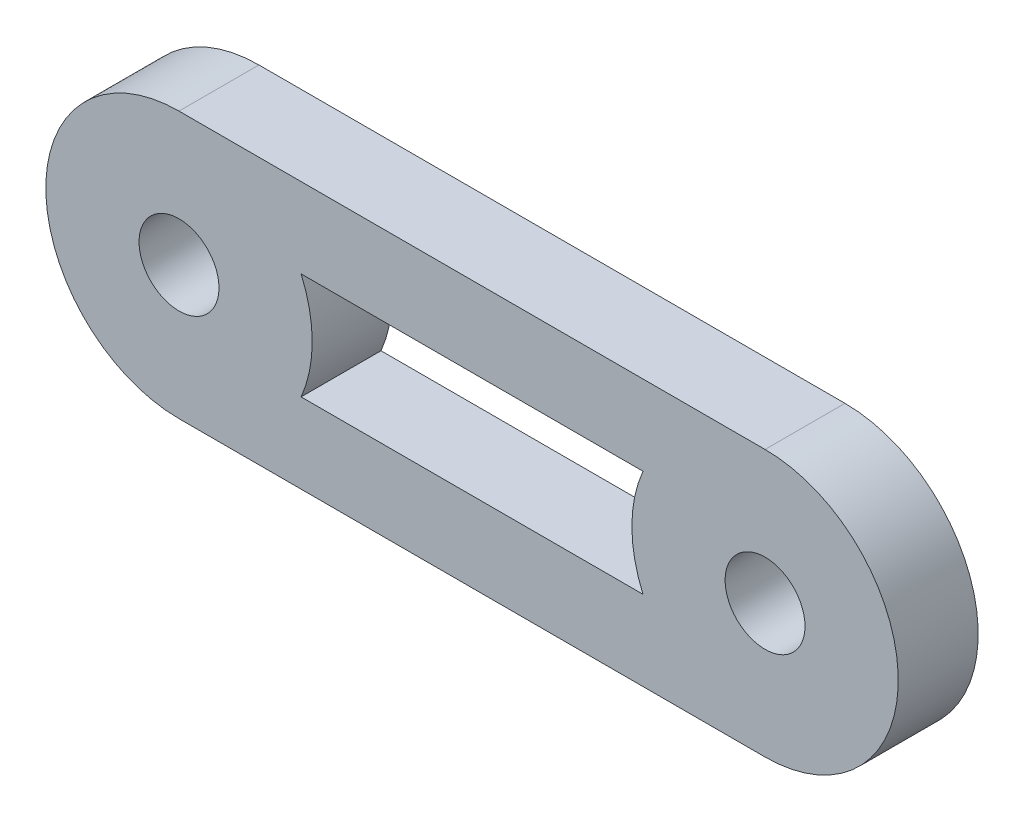
SolidWorks part; units mm, degrees
material "Plain Carbon Steel"
ref_plane "Front Plane" through (0, 0, 0) normal (0, 0, 1) x (1, 0, 0)
ref_plane "Top Plane" through (0, 0, 0) normal (0, 1, 0) x (1, 0, 0)
ref_plane "Right Plane" through (0, 0, 0) normal (1, 0, 0) x (0, 0, -1)
sketch "Sketch1" plane through (0, 0, 0) normal (0, 0, 1) x (1, 0, 0)
  line L0 (0, 0) -> (22, 0)
  line L1 (0, -5) -> (22, -5)
  line L2 (0, 5) -> (22, 5)
  circle A0 centre (22, 0) radius 1.5
  circle A1 centre (0, 0) radius 1.5
  arc A2 (0, -5) -> (0, 5) centre (0, 0) cw
  arc A3 (22, -5) -> (22, 5) centre (22, 0) ccw
  dimension "D1" = 3
extrude "Extrude1" add sketch "Sketch1" along normal blind 3 contours L1 A3 L2 A2 A1 A0 region at (-4.6647, 0, 0)
sketch "Sketch2" plane through (0, 0, 3) normal (0, 0, 1) x (1, 0, 0)
  line L4 (0, -2) -> (22, -2)
  line L5 (22, 2) -> (0, 2)
  line L6 (4.5826, -2) -> (17.4174, -2)
  line L7 (17.4174, 2) -> (4.5826, 2)
  arc A2 (4.5826, -2) -> (4.5826, 2) centre (0, 0) ccw
  arc A3 (17.4174, 2) -> (17.4174, -2) centre (22, 0) ccw
  arc A4 (22, -2) -> (22, 2) centre (22, 0) ccw
  arc A5 (0, 2) -> (0, -2) centre (0, 0) ccw
  dimension "D1" = 3
extrude "Cut-Extrude1" cut sketch "Sketch2" against normal blind 10
move or copy body "Body-Move/Copy1" [suppressed] bodies to move or copy 103
move or copy body "Body-Move/Copy2" [suppressed] bodies to move or copy 103
move or copy body "Body-Move/Copy3" [suppressed] bodies to move or copy 103
